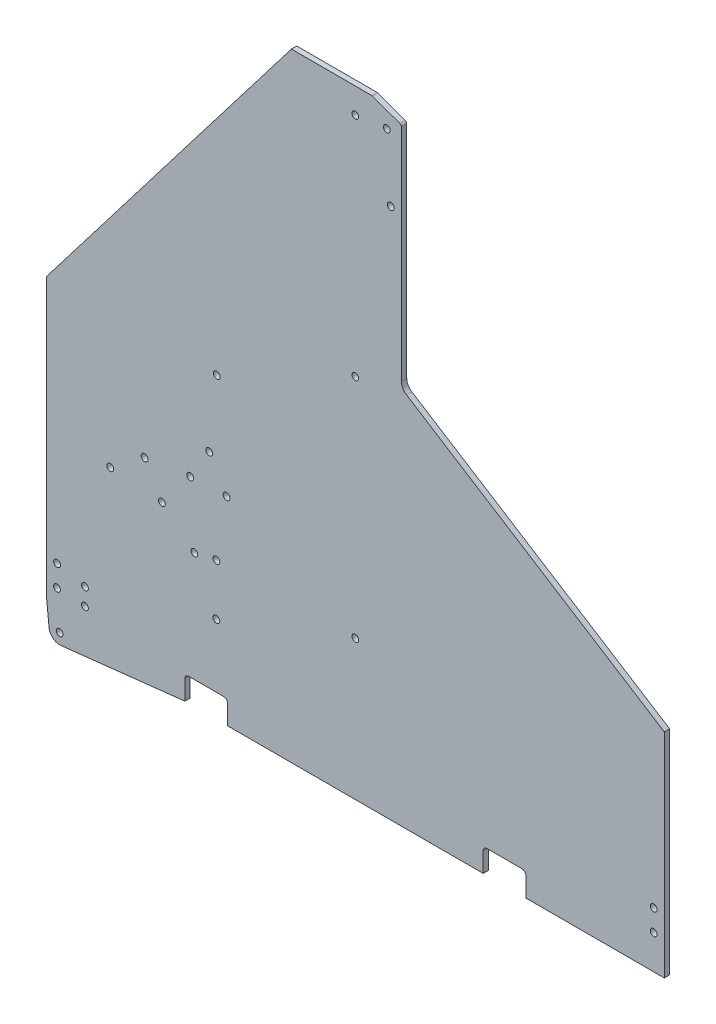
SolidWorks part; units mm, degrees
ref_plane "Front Plane" through (0, 0, 0) normal (0, 0, 1) x (1, 0, 0)
ref_plane "Top Plane" through (0, 0, 0) normal (0, 1, 0) x (1, 0, 0)
ref_plane "Right Plane" through (0, 0, 0) normal (1, 0, 0) x (0, 0, -1)
sketch "Sketch1" plane through (0, 0, 0) normal (0, 0, 1) x (1, 0, 0)
  line L0 (82.55, -20.32) -> (82.55, -6.35)
  line L2 (0, 0) -> (0, 157.48)
  line L4 (368.3, -20.32) -> (368.3, 106.68)
  line L5 (82.55, -6.35) -> (107.95, -6.35)
  line L6 (107.95, -6.35) -> (107.95, -20.32)
  line L7 (107.95, -20.32) -> (260.35, -20.32)
  line L8 (260.35, -20.32) -> (260.35, -6.35)
  line L9 (260.35, -6.35) -> (285.75, -6.35)
  line L10 (285.75, -6.35) -> (285.75, -20.32)
  line L11 (285.75, -20.32) -> (368.3, -20.32)
  line L12 (361.95, 12.7) -> (368.3, 12.7) construction
  line L13 (0, 0) -> (6.35, 0) construction
  line L14 (0.0315, -6.9818) -> (1.619, -22.8568)
  line L15 (8.6391, -28.5361) -> (82.55, -20.32)
  line L16 (0, 0) -> (0, -6.35)
  line L17 (85.725, 97.155) -> (82.9754, 95.5675) construction
  line L18 (97.0634, 115.6163) -> (58.5686, 93.3913) construction
  line L19 (97.0634, 115.6163) -> (107.3822, 97.7437) construction
  line L20 (58.5686, 93.3913) -> (68.8873, 75.5187) construction
  line L21 (107.3822, 97.7437) -> (68.8873, 75.5187) construction
  line L22 (97.0634, 115.6163) -> (68.8873, 75.5187) construction
  line L23 (58.5686, 93.3913) -> (107.3822, 97.7437) construction
  line L24 (7.9375, -22.225) -> (88.2169, 59.1366) construction
  line L25 (184.15, 62.98) -> (184.15, 197.98) construction
  line L26 (184.15, 197.98) -> (184.15, 332.98) construction
  line L27 (355.6, 335.28) -> (330.2, 335.28) construction
  line L28 (330.2, 335.28) -> (330.2, 220.98) construction
  line L29 (330.2, 220.98) -> (355.6, 220.98) construction
  line L30 (355.6, 220.98) -> (355.6, 335.28) construction
  line L31 (184.15, 347.98) -> (184.15, 269.4703) construction
  line L32 (12.7, 335.28) -> (38.1, 335.28) construction
  line L33 (38.1, 335.28) -> (38.1, 220.98) construction
  line L34 (12.7, 220.98) -> (12.7, 335.28) construction
  line L35 (38.1, 220.98) -> (12.7, 220.98) construction
  line L36 (194.15, 347.98) -> (211.6138, 341.63)
  line L37 (184.15, 347.98) -> (146.05, 347.98)
  line L38 (184.15, 347.98) -> (194.15, 347.98)
  line L39 (348.5362, 347.98) -> (413.4623, 347.98)
  line L40 (348.5362, 347.98) -> (211.6138, 347.98) construction
  line L42 (146.05, 347.98) -> (0, 157.48)
  line L44 (211.6138, 341.63) -> (211.6138, 205.74)
  line L45 (211.6138, 205.74) -> (368.3, 106.68)
  line L46 (194.15, 347.98) -> (-141.0713, 347.98) construction
  circle A0 centre (6.35, 0) radius 2.032
  circle A1 centre (6.35, 12.7) radius 2.032
  circle A2 centre (361.95, 0) radius 2.032
  circle A3 centre (361.95, 12.7) radius 2.032
  arc A5 (1.619, -22.8568) -> (8.6391, -28.5361) centre (7.9375, -22.225) ccw
  circle A6 centre (7.9375, -22.225) radius 2.032
  arc A7 (0, -6.35) -> (0.0315, -6.9818) centre (6.35, -6.35) ccw
  circle A8 centre (38.1, 78.105) radius 2.032
  circle A9 centre (85.725, 97.155) radius 2.032
  circle A10 centre (58.5686, 93.3913) radius 2.032
  circle A11 centre (68.8873, 75.5187) radius 2.032
  circle A12 centre (107.3822, 97.7437) radius 2.032
  circle A13 centre (97.0634, 115.6163) radius 2.032
  circle A14 centre (88.2169, 59.1366) radius 2.032
  circle A15 centre (184.15, 62.98) radius 2
  circle A16 centre (184.15, 197.98) radius 2
  circle A17 centre (184.15, 332.98) radius 2
  circle A18 centre (63.5, 316.23) radius 2.032
  circle A19 centre (101.6, 157.48) radius 2.032
  circle A20 centre (355.6, 335.28) radius 2.032
  circle A21 centre (330.2, 335.28) radius 2.032
  circle A22 centre (355.6, 220.98) radius 2.032
  circle A23 centre (330.2, 220.98) radius 2.032
  circle A24 centre (12.7, 335.28) radius 2.032
  circle A25 centre (38.1, 335.28) radius 2.032
  circle A26 centre (12.7, 220.98) radius 2.032
  circle A27 centre (38.1, 220.98) radius 2.032
  circle A28 centre (202.8819, 335.28) radius 2
  circle A29 centre (205.2638, 296.418) radius 2.032
  point P82 (184.15, 347.98)
  point P83 (202.8819, 344.805)
  dimension "D6" = 4.064
  dimension "D10" = 6.35
  dimension "D11" = 4.064
  dimension "D17" = 38.1
  dimension "D27" = 4
  dimension "D31" = 4.064
  dimension "D32" = 38.1
  dimension "D36" = 4.064
  dimension "D47" = 45.212
  dimension "D48" = 4.064
  dimension "D2" = 127
  dimension "D3" = 13.97
  dimension "D4" = 25.4
  dimension "D5" = 152.4
  dimension "D7" = 12.7
  dimension "D8" = 6.35
  dimension "D9" = 20.32
  dimension "D12" = 22.225
  dimension "D13" = 1.5875
  dimension "D14" = 82.55
  dimension "D15" = 368.3
  dimension "D16" = 6.35
  dimension "D18" = 98.425
  dimension "D19" = 47.625
  dimension "D20" = 19.05
  dimension "D21" = 3.175
  dimension "D22" = 60
  dimension "D23" = 20.6375
  dimension "D24" = 44.45
  dimension "D25" = 38.1
  dimension "D26" = 114.3
  dimension "D28" = 135
  dimension "D29" = 12.7
  dimension "D30" = 15
  dimension "D33" = 63.5
  dimension "D34" = 27.4638
  dimension "D35" = 101.6
  dimension "D37" = 114.3
  dimension "D38" = 25.4
  dimension "D39" = 12.7
  dimension "D40" = 157.48
  dimension "D41" = 142.24
  dimension "D42" = 368.3
  dimension "D43" = 10
  dimension "D44" = 6.35
  dimension "D45" = 31.75
  dimension "D46" = 6.35
  dimension "D49" = 6.35
extrude "Boss-Extrude1" add sketch "Sketch1" along normal blind 3.175 contours L16 A7 L14 A5 L15 L0 L5 L6 L7 L8 L9 L10 L11 L4 L42 L2 A19 A17 A16 A15 A14 A13 A12 A11 A10 A9 A8 A0 A1 A2 A3 A6 region at (167.243, 117.6611, 0)
fillet "Fillet1" radius 2.286 4 edges at (285.75, -6.35, 1.5875) (107.95, -6.35, 1.5875) (260.35, -6.35, 1.5875) (82.55, -6.35, 1.5875)
fillet "Fillet2" radius 6.35 1 edges at (211.6138, 205.74, 1.5875)
sketch "Sketch2" plane through (0, 0, 0) normal (0, 0, -1) x (-1, 0, 0)
  circle A0 centre (-101.3398, 61.8475) radius 2.032 construction
  circle A1 centre (-101.3398, 31.3675) radius 2.032 construction
  circle A2 centre (-23.012, 8.964) radius 2.032 construction
  circle A3 centre (-23.012, -1.196) radius 2.032 construction
  circle A4 centre (-101.3398, 61.8475) radius 2.032
  circle A5 centre (-101.3398, 31.3675) radius 2.032
  circle A6 centre (-23.012, 8.964) radius 2.032
  circle A7 centre (-23.012, -1.196) radius 2.032
extrude "Cut-Extrude1" cut sketch "Sketch2" against normal through all
fillet "Fillet3" radius 1.5875 2 edges at (211.6138, 341.63, 1.5875) (194.15, 347.98, 1.5875)
